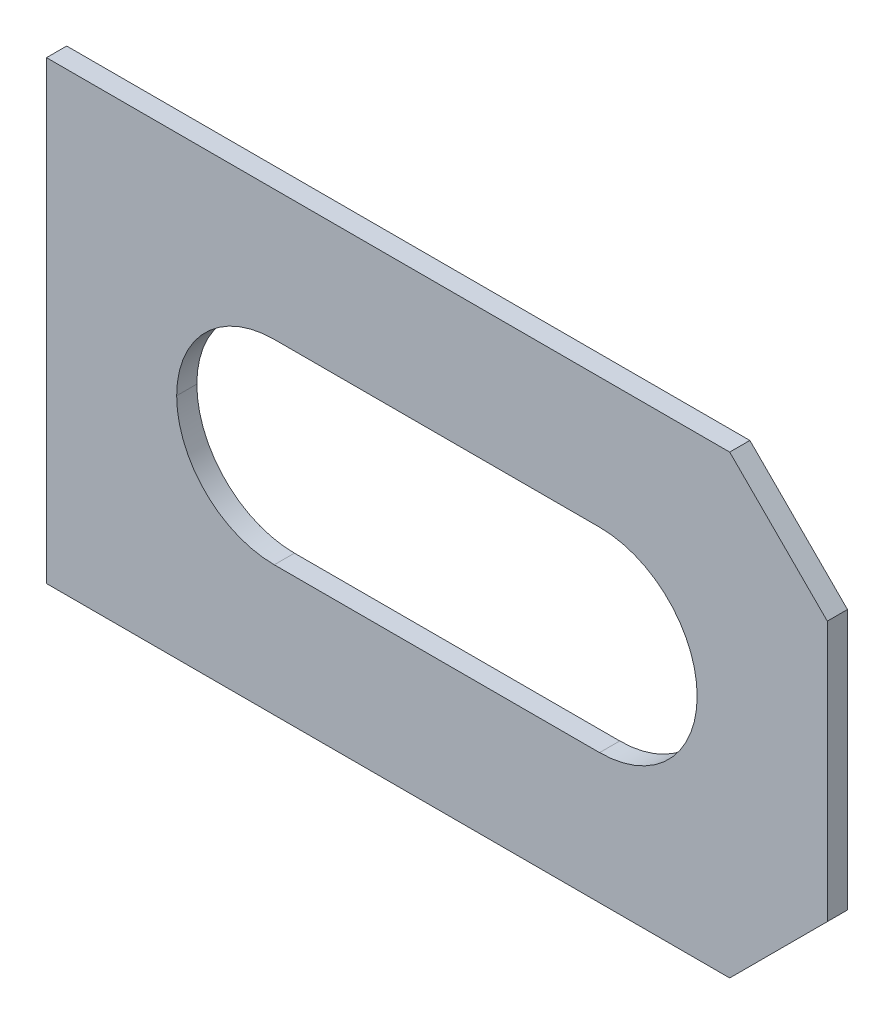
SolidWorks part; units mm, degrees
material "Teak"
ref_plane "Front Plane" through (0, 0, 0) normal (0, 0, 1) x (1, 0, 0)
ref_plane "Top Plane" through (0, 0, 0) normal (0, 1, 0) x (1, 0, 0)
ref_plane "Right Plane" through (0, 0, 0) normal (1, 0, 0) x (0, 0, -1)
sketch "Sketch1" plane through (0, 0, 0) normal (0, 0, 1) x (1, 0, 0)
  line L1 (-60, -35) -> (60, -35)
  line L2 (-60, -35) -> (-60, 35)
  line L3 (-60, 35) -> (60, 35)
  line L4 (60, -35) -> (60, 35)
  line L5 (-60, -35) -> (60, 35) construction
  line L6 (-60, 35) -> (60, -35) construction
  line L7 (-40, -15) -> (40, -15)
  line L8 (-40, -15) -> (-40, 15)
  line L9 (-40, 15) -> (40, 15)
  line L10 (40, -15) -> (40, 15)
  line L11 (-40, -15) -> (40, 15) construction
  line L12 (-40, 15) -> (40, -15) construction
  point P0 (0, 0)
  point P6 (0, 0)
  dimension "D1" = 70
  dimension "D2" = 120
  dimension "D3" = 20
  dimension "D4" = 20
extrude "Boss-Extrude1" add sketch "Sketch1" along normal blind 3.1
fillet "Fillet1" radius 15 4 edges at (40, -15, 1.55) (40, 15, 1.55) (-40, 15, 1.55) (-40, -15, 1.55)
chamfer "Chamfer1" distance 15 angle 45 2 edges at (60, -35, 1.55) (60, 35, 1.55)
